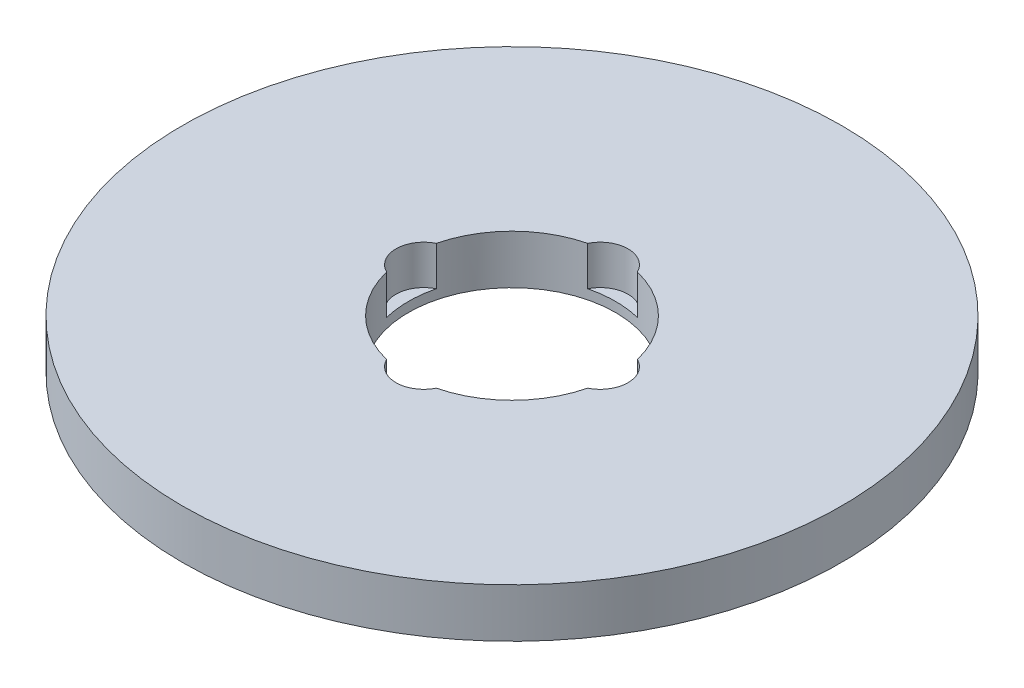
SolidWorks part; units mm, degrees
ref_plane "Front Plane" through (0, 0, 0) normal (0, 0, 1) x (1, 0, 0)
ref_plane "Top Plane" through (0, 0, 0) normal (0, 1, 0) x (1, 0, 0)
ref_plane "Right Plane" through (0, 0, 0) normal (1, 0, 0) x (0, 0, -1)
sketch "Sketch1" plane through (0, 0, 0) normal (0, 1, 0) x (1, 0, 0)
  circle A0 centre (0, 0) radius 87.5
  dimension "FLANGE_OD" = 175
extrude "Boss-Extrude1" add sketch "Sketch1" along normal blind 13
sketch "Sketch2" plane through (0, 0, 0) normal (0, 1, 0) x (1, 0, 0)
  circle A0 centre (0, 0) radius 27.5
  dimension "BORE_D" = 55
extrude "Cut-Extrude1" cut sketch "Sketch2" along normal through all
sketch "Sketch3" plane through (0, 13, 0) normal (0, 1, 0) x (1, 0, 0)
  circle A0 centre (0, 0) radius 23.4494 construction
  circle A1 centre (-23.4494, 0) radius 7.3485
  dimension "BOLT_D" = 14.6969
  dimension "BOLT_PCD" = 46.8987
extrude "Cut-Extrude2" cut sketch "Sketch3" against normal blind 10.4451
pattern_circular "CirPattern1" count 4 over 360 about axis through (0, 0, 0) along (0, 1, 0) of "Cut-Extrude2"
